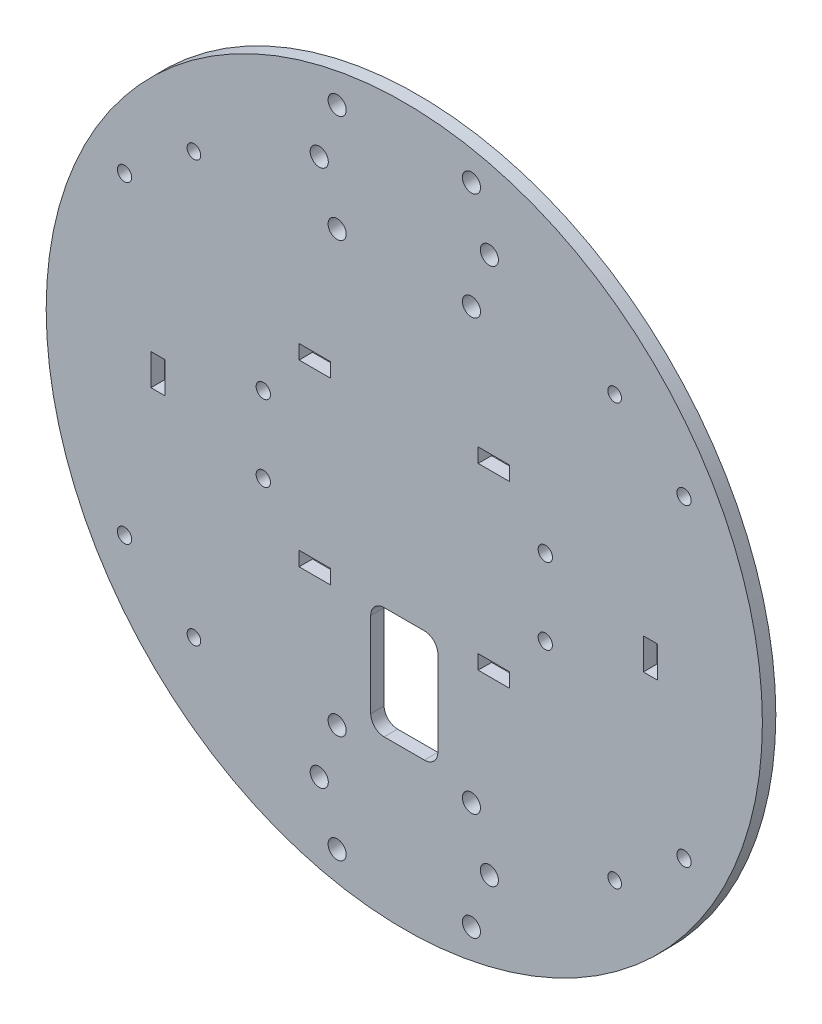
SolidWorks part; units mm, degrees
ref_plane "前视基准面" through (0, 0, 0) normal (0, 0, 1) x (1, 0, 0)
ref_plane "上视基准面" through (0, 0, 0) normal (0, 1, 0) x (1, 0, 0)
ref_plane "右视基准面" through (0, 0, 0) normal (1, 0, 0) x (0, 0, -1)
sketch "草图1" plane through (0, 0, 0) normal (0, 0, 1) x (1, 0, 0)
  line L0 (0, 0) -> (-47, 47) construction
  line L1 (50, 50) -> (-50, 50) construction
  line L2 (-50, 50) -> (-50, -50) construction
  line L3 (-50, -50) -> (50, -50) construction
  line L4 (50, -50) -> (50, 50) construction
  line L9 (-50, 50) -> (-47, 50) construction
  line L10 (-50, 50) -> (-50, 47) construction
  line L11 (-50, 47) -> (-47, 47) construction
  line L12 (-47, 50) -> (-47, 47) construction
  line L13 (0, 0) -> (47, 47) construction
  line L14 (0, 0) -> (0, 171.8985) construction
  line L15 (0, -45) -> (7.5, -45) construction
  line L16 (0, -45) -> (0, -50) construction
  line L17 (0, -50) -> (7.5, -50) construction
  line L18 (7.5, -45) -> (7.5, -50) construction
  line L19 (-7.5, -20) -> (7.5, -20)
  line L20 (-7.5, -20) -> (-7.5, -45)
  line L21 (-7.5, -45) -> (7.5, -45)
  line L22 (7.5, -20) -> (7.5, -45)
  line L25 (0, 60) -> (19, 60) construction
  line L26 (0, 0) -> (43.586, 0) construction
  line L27 (-15, 48) -> (15, 48) construction
  line L28 (-15, 48) -> (-15, 72) construction
  line L29 (-15, 72) -> (15, 72) construction
  line L30 (15, 48) -> (15, 72) construction
  line L31 (-15, 48) -> (15, 72) construction
  line L32 (-15, 72) -> (15, 48) construction
  line L34 (-62.5, -35) -> (62.5, -35) construction
  line L35 (-62.5, -35) -> (-62.5, 35) construction
  line L36 (-62.5, 35) -> (62.5, 35) construction
  line L37 (62.5, -35) -> (62.5, 35) construction
  line L38 (-62.5, -35) -> (62.5, 35) construction
  line L39 (-62.5, 35) -> (62.5, -35) construction
  line L40 (-31.5, -8.5) -> (31.5, -8.5) construction
  line L41 (-31.5, -8.5) -> (-31.5, 8.5) construction
  line L42 (-31.5, 8.5) -> (31.5, 8.5) construction
  line L43 (31.5, -8.5) -> (31.5, 8.5) construction
  line L44 (-31.5, -8.5) -> (31.5, 8.5) construction
  line L45 (-31.5, 8.5) -> (31.5, -8.5) construction
  circle A0 centre (0, 0) radius 80
  circle A2 centre (-47, 47) radius 1.52
  circle A3 centre (0, 0) radius 50 construction
  circle A4 centre (47, 47) radius 1.52
  circle A5 centre (47, -47) radius 1.52
  circle A6 centre (-47, -47) radius 1.52
  circle A7 centre (19, 60) radius 2.025
  circle A8 centre (15, 72) radius 2.025
  circle A9 centre (15, 48) radius 2.025
  circle A10 centre (-15, 48) radius 2.025
  circle A11 centre (-19, 60) radius 2.025
  circle A12 centre (-15, 72) radius 2.025
  circle A13 centre (15, -48) radius 2.025
  circle A14 centre (15, -72) radius 2.025
  circle A15 centre (19, -60) radius 2.025
  circle A16 centre (-15, -48) radius 2.025
  circle A17 centre (-19, -60) radius 2.025
  circle A18 centre (-15, -72) radius 2.025
  circle A19 centre (-62.5, 35) radius 1.6
  circle A20 centre (-62.5, -35) radius 1.6
  circle A21 centre (-31.5, 8.5) radius 1.6
  circle A22 centre (-31.5, -8.5) radius 1.6
  circle A23 centre (31.5, -8.5) radius 1.6
  circle A24 centre (31.5, 8.5) radius 1.6
  circle A25 centre (62.5, 35) radius 1.6
  circle A26 centre (62.5, -35) radius 1.6
  point P11 (0, -50)
  point P29 (0, 60)
  dimension "D1" = 160
  dimension "D2" = 100
  dimension "D5" = 3.04
  dimension "D14" = 4.05
  dimension "D17" = 4.05
  dimension "D18" = 4.05
  dimension "D21" = 3.2
  dimension "D22" = 3.2
  dimension "D25" = 3.2
  dimension "D26" = 3.2
  dimension "D3" = 3
  dimension "D4" = 3
  dimension "D6" = 4
  dimension "D7" = 90
  dimension "D8" = 5
  dimension "D9" = 7.5
  dimension "D10" = 15
  dimension "D11" = 25
  dimension "D12" = 60
  dimension "D13" = 19
  dimension "D15" = 30
  dimension "D16" = 24
  dimension "D19" = 125
  dimension "D20" = 70
  dimension "D23" = 63
  dimension "D24" = 17
extrude "凸台-拉伸1" add sketch "草图1" along normal blind 3
sketch "电池扎带草图" plane through (0, 0, 0) normal (0, 0, 1) x (1, 0, 0)
  line L0 (0, 0) -> (55, 0) construction
  line L1 (-20, -20) -> (20, -20) construction
  line L2 (-20, -20) -> (-20, 20) construction
  line L3 (-20, 20) -> (20, 20) construction
  line L4 (20, -20) -> (20, 20) construction
  line L5 (-20, -20) -> (20, 20) construction
  line L6 (-20, 20) -> (20, -20) construction
  line L7 (16.5, -18.4) -> (23.5, -18.4)
  line L8 (16.5, 18.4) -> (23.5, 18.4)
  line L9 (16.5, 18.4) -> (16.5, 21.6)
  line L10 (16.5, 21.6) -> (23.5, 21.6)
  line L11 (23.5, 18.4) -> (23.5, 21.6)
  line L12 (16.5, 18.4) -> (23.5, 21.6) construction
  line L13 (16.5, 21.6) -> (23.5, 18.4) construction
  line L14 (16.5, -18.4) -> (16.5, -21.6)
  line L15 (16.5, -21.6) -> (23.5, -21.6)
  line L16 (23.5, -18.4) -> (23.5, -21.6)
  line L17 (0, 0) -> (0, -16.0006) construction
  line L18 (53.4, 3.5) -> (56.6, 3.5)
  line L19 (53.4, 3.5) -> (53.4, -3.5)
  line L20 (53.4, -3.5) -> (56.6, -3.5)
  line L21 (56.6, 3.5) -> (56.6, -3.5)
  line L22 (53.4, 3.5) -> (56.6, -3.5) construction
  line L23 (53.4, -3.5) -> (56.6, 3.5) construction
  line L24 (-16.5, 21.6) -> (-23.5, 21.6)
  line L25 (-23.5, 18.4) -> (-23.5, 21.6)
  line L26 (-16.5, 18.4) -> (-23.5, 18.4)
  line L27 (-16.5, 18.4) -> (-16.5, 21.6)
  line L28 (-53.4, -3.5) -> (-56.6, -3.5)
  line L29 (-56.6, 3.5) -> (-56.6, -3.5)
  line L30 (-53.4, 3.5) -> (-56.6, 3.5)
  line L31 (-53.4, 3.5) -> (-53.4, -3.5)
  line L32 (-16.5, -18.4) -> (-16.5, -21.6)
  line L33 (-16.5, -21.6) -> (-23.5, -21.6)
  line L34 (-23.5, -18.4) -> (-23.5, -21.6)
  line L35 (-16.5, -18.4) -> (-23.5, -18.4)
  line L36 (0, 55) -> (0, 0) construction
  line L45 (-12, 75.25) -> (12, 75.25) construction
  line L46 (-12, 75.25) -> (-12, 34.75) construction
  line L47 (-12, 34.75) -> (12, 34.75) construction
  line L48 (12, 75.25) -> (12, 34.75) construction
  line L49 (-12, 75.25) -> (12, 34.75) construction
  line L50 (-12, 34.75) -> (12, 75.25) construction
  point P0 (0, 0)
  point P35 (0, 0)
  point P48 (0, 55)
  dimension "D1" = 40
  dimension "D2" = 40
  dimension "D3" = 55
  dimension "D4" = 7
  dimension "D5" = 3.2
  dimension "D6" = 3.2
  dimension "D7" = 7
  dimension "D10" = 55
  dimension "D11" = 24
  dimension "D12" = 40.5
extrude "电池+BB响扎带孔位" cut sketch "电池扎带草图" along normal blind 3
fillet "圆角1" radius 3 4 edges at (-7.5, -45, 1.5) (7.5, -45, 1.5) (-7.5, -20, 1.5) (7.5, -20, 1.5)
